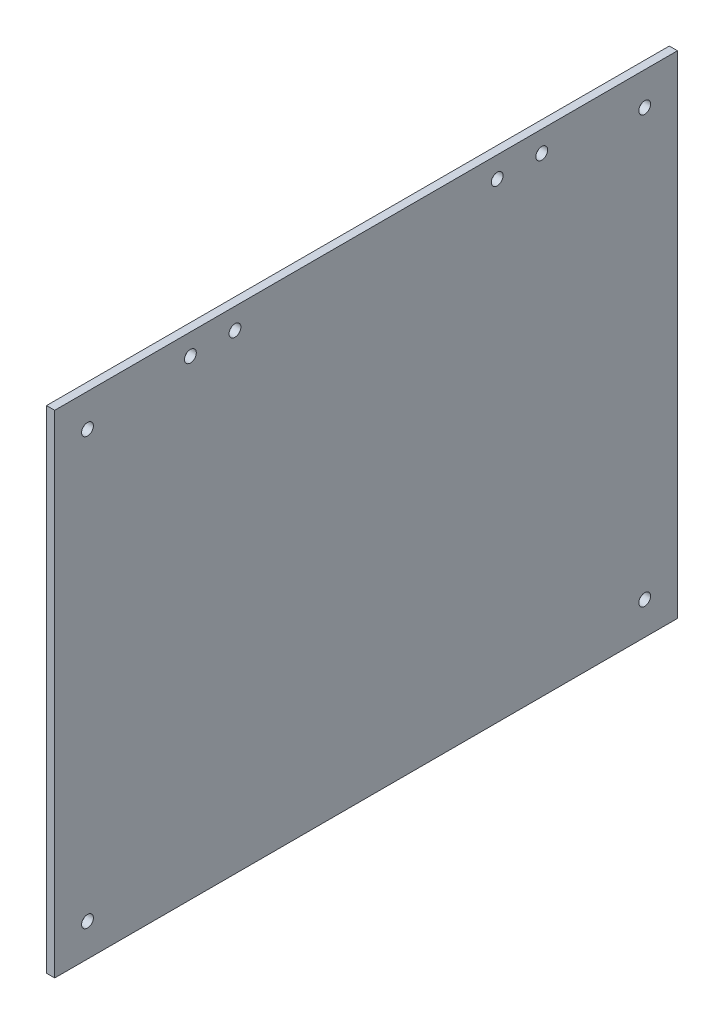
SolidWorks part; units mm, degrees
ref_plane "Front Plane" through (0, 0, 0) normal (0, 0, 1) x (1, 0, 0)
ref_plane "Top Plane" through (0, 0, 0) normal (0, 1, 0) x (1, 0, 0)
ref_plane "Right Plane" through (0, 0, 0) normal (1, 0, 0) x (0, 0, -1)
sketch "Sketch1" plane through (0, 0, 0) normal (1, 0, 0) x (0, 0, -1)
  line L1 (0, 0) -> (241.3, 0)
  line L2 (0, 0) -> (0, 190.5)
  line L3 (0, 190.5) -> (241.3, 190.5)
  line L4 (241.3, 0) -> (241.3, 190.5)
  dimension "D1" = 241.3
  dimension "D2" = 190.5
extrude "Boss-Extrude1" add sketch "Sketch1" along normal blind 3.175
sketch "Sketch2" plane through (3.175, 0, 0) normal (1, 0, 0) x (0, 0, -1)
  line L2 (-1000, 95.25) -> (49000, 95.25) construction
  line L3 (0, 190.5) -> (0, 0) construction
  line L4 (120.65, -809.5) -> (120.65, 49190.5) construction
  line L5 (241.3, 190.5) -> (0, 190.5) construction
  line L6 (1228.6, 95.25) -> (-48771.4, 95.25) construction
  line L7 (0, 0) -> (241.3, 0) construction
  line L8 (241.3, 0) -> (241.3, 190.5) construction
  circle A8 centre (228.6, 12.7) radius 2.286
  circle A9 centre (228.6, 177.8) radius 2.286
  circle A10 centre (12.7, 12.7) radius 2.286
  circle A11 centre (12.7, 177.8) radius 2.286
  point P15 (0, 95.25)
  point P20 (120.65, 190.5)
  dimension "D1" = 4.572
  dimension "D2" = 12.7
  dimension "D3" = 12.7
extrude "Cut-Extrude1" cut sketch "Sketch2" against normal through all
sketch "Sketch3" plane through (3.175, 0, 0) normal (1, 0, 0) x (0, 0, -1)
  line L0 (54.864, 182.372) -> (67.564, 182.372) construction
  line L1 (173.736, 182.372) -> (186.436, 182.372) construction
  line L2 (241.3, 190.5) -> (0, 190.5) construction
  circle A0 centre (52.578, 182.372) radius 2.286
  circle A1 centre (69.85, 182.372) radius 2.286
  circle A2 centre (171.45, 182.372) radius 2.286
  circle A3 centre (188.722, 182.372) radius 2.286
  point P14 (120.65, 190.5)
  dimension "D2" = 4.572
  dimension "D1" = 12.7
  dimension "D3" = 12.7
  dimension "D4" = 8.128
  dimension "D5" = 50.8
  dimension "D6" = 50.8
extrude "Cut-Extrude2" cut sketch "Sketch3" against normal through all
